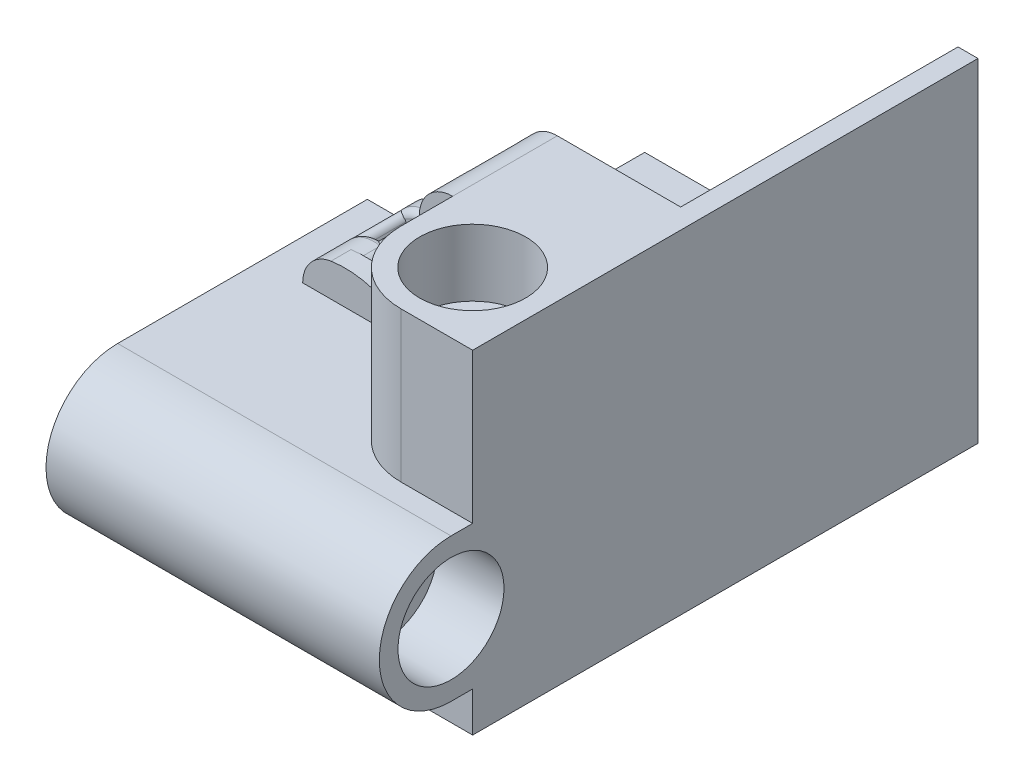
SolidWorks part; units mm, degrees
material "ABS"
ref_plane "Front Plane" through (0, 0, 0) normal (0, 0, 1) x (1, 0, 0)
ref_plane "Top Plane" through (0, 0, 0) normal (0, 1, 0) x (1, 0, 0)
ref_plane "Right Plane" through (0, 0, 0) normal (1, 0, 0) x (0, 0, -1)
sketch "Sketch1" plane through (0, 0, 0) normal (0, 0, 1) x (1, 0, 0)
  line L1 (-25, -25) -> (25, -25)
  line L2 (-25, -25) -> (-25, 25)
  line L3 (-25, 25) -> (25, 25)
  line L4 (25, -25) -> (25, 25)
  line L5 (-25, -25) -> (25, 25) construction
  line L6 (-25, 25) -> (25, -25) construction
  point P0 (0, 0)
  dimension "D1" = 50
  dimension "D2" = 50
extrude "Boss-Extrude1" add sketch "Sketch1" along normal blind 5
sketch "Sketch2" plane through (0, 0, 0) normal (0, 1, 0) x (1, 0, 0)
  line L0 (14.25, -15.75) -> (25, -15.75) construction
  line L1 (3.5, -5) -> (25, -5)
  line L2 (25, -5) -> (-25, -5) construction
  line L3 (25, -5) -> (25, 0) construction
  line L4 (25, -15.75) -> (25, -5)
  line L5 (3.5, -15.75) -> (3.5, -5)
  line L6 (25, -15.75) -> (25, -26.5)
  line L7 (25, -26.5) -> (14.25, -26.5)
  arc A1 (3.5, -15.75) -> (14.25, -26.5) centre (14.25, -15.75) ccw
  dimension "D2" = 21.5
extrude "Boss-Extrude2" add sketch "Sketch2" along normal up to surface and the other way up to surface up to face at (0, 25, 2.5) other way up to face at (0, -25, 2.5)
ref_axis "Axis1" through (14.25, 25, 15.75) along (0, -1, 0)
sketch "Sketch3" plane through (0, 0, 0) normal (1, 0, 0) x (0, 0, -1)
  line L0 (-29.75, 2.5) -> (-5, 2.5)
  line L1 (-5, 25) -> (-5, -25) construction
  line L2 (-29.75, -19) -> (-5, -19)
  line L3 (-5, 25) -> (-5, -25) construction
  line L4 (-5, -19) -> (-5, 2.5)
  line L5 (-15.75, 25) -> (-15.75, -25) construction
  line L6 (-15.75, -25) -> (-5, -25) construction
  arc A0 (-29.75, 2.5) -> (-29.75, -19) centre (-29.75, -8.25) ccw
  dimension "D1" = 21.5
  dimension "D2" = 14
  dimension "D3" = 6
extrude "Boss-Extrude3" add sketch "Sketch3" along normal up to surface and the other way up to surface up to face at (25, 0, 13.25) other way up to face at (-25, 0, 2.5)
ref_axis "Axis2" through (25, -8.25, 29.75) along (-1, 0, 0)
sketch "Sketch4" plane through (0, -25, 0) normal (0, -1, 0) x (1, 0, 0)
  circle A0 centre (14.25, 15.75) radius 5
  dimension "D1" = 10
extrude "Cut-Extrude1" cut sketch "Sketch4" against normal up to surface (50 mm away) up to face at (4.7534, 25, 12.3359)
sketch "Sketch5" plane through (0, -25, 0) normal (0, -1, 0) x (1, 0, 0)
  circle A0 centre (14.25, 15.75) radius 7.95
  dimension "D1" = 15.9
extrude "Cut-Extrude2" cut sketch "Sketch5" against normal blind 10
sketch "Sketch6" plane through (0, 25, 0) normal (0, 1, 0) x (1, 0, 0)
  circle A0 centre (14.25, -15.75) radius 7.95
  dimension "D1" = 15.9
extrude "Cut-Extrude3" cut sketch "Sketch6" against normal blind 10
sketch "Sketch7" plane through (25, 0, 0) normal (1, 0, 0) x (0, 0, -1)
  circle A0 centre (-29.75, -8.25) radius 5
  dimension "D1" = 10
extrude "Cut-Extrude4" cut sketch "Sketch7" against normal up to surface (50 mm away) up to face at (-25, -4.125, 11.2812)
sketch "Sketch8" plane through (25, 0, 0) normal (1, 0, 0) x (0, 0, -1)
  circle A0 centre (-29.75, -8.25) radius 7.95
  dimension "D1" = 15.9
extrude "Cut-Extrude5" cut sketch "Sketch8" against normal blind 10
sketch "Sketch9" plane through (-25, 0, 0) normal (-1, 0, 0) x (0, 0, 1)
  circle A0 centre (29.75, -8.25) radius 7.95
  dimension "D1" = 15.9
extrude "Cut-Extrude6" cut sketch "Sketch9" against normal blind 10
sketch "Sketch10" plane through (0, 0, 5) normal (0, 0, 1) x (1, 0, 0)
  line L0 (3.5, 2.5) -> (-5, 11) construction
  line L1 (3.5, 25) -> (-25, 25)
  line L2 (-25, 2.5) -> (-19, 2.5)
  line L4 (-25, 2.5) -> (3.5, 2.5)
  line L5 (3.5, 2.5) -> (3.5, 25)
  line L6 (3.5, 25) -> (-25, 25)
  line L7 (-25, 25) -> (-25, 2.5)
  line L8 (-25, 2.5) -> (3.5, 2.5)
  line L9 (3.5, 2.5) -> (3.5, 25)
  line L10 (3.5, 25) -> (-25, 25)
  line L11 (-25, 25) -> (-25, 2.5)
  arc A0 (-11.7656, 6.5462) -> (-0.5462, 17.7656) centre (-5, 11) ccw
  arc A1 (3.5, 25) -> (-1.4109, 19.0603) centre (3.5, 20) ccw
  arc A2 (-0.5462, 17.7656) -> (-1.4109, 19.0603) centre (0.5535, 19.4362) cw
  arc A3 (-19, 2.5) -> (-13.0603, 7.4109) centre (-14, 2.5) cw
  arc A4 (-11.7656, 6.5462) -> (-13.0603, 7.4109) centre (-13.4362, 5.4465) ccw
  line M5 (-25, 2.5) -> (3.5, 2.5)
  line M7 (3.5, 25) -> (-25, 25)
  line M8 (-25, 25) -> (-25, 2.5)
  dimension "D2" = 16.2
  dimension "D3" = 5
  dimension "D4" = 2
  dimension "D1" = 0
extrude "Cut-Extrude7" cut sketch "Sketch10" against normal up to surface (5 mm away) contours A4 A0 A2 A1 A3 M7 M8 M5 region at (-11.9115, 14.3488, 5) up to face at (0, 0, 0)
sketch "Sketch11" plane through (0, 0, 5) normal (0, 0, 1) x (1, 0, 0)
  line L0 (3.5, 2.5) -> (-5, 11) construction
  line L1 (3.5, 25) -> (3.5, 2.5) construction
  line L2 (3.5, 2.5) -> (-19, 2.5) construction
  line L3 (3.5, 25) -> (3.5, 2.5)
  line L4 (3.5, 2.5) -> (-19, 2.5)
  arc A0 (-7.0104, 6.422) -> (-0.422, 13.0104) centre (-5, 11) ccw
  arc A1 (-1.4425, 20.7559) -> (-0.422, 13.0104) centre (12.3966, 18.6394) ccw
  arc A2 (-14.7559, 7.4425) -> (-7.0104, 6.422) centre (-12.6394, -6.3966) cw
  arc A4 (3.5, 25) -> (-1.4109, 19.0603) centre (3.5, 20) ccw construction
  arc A10 (-13.0603, 7.4109) -> (-19, 2.5) centre (-14, 2.5) ccw construction
  arc A11 (3.5, 25) -> (-1.4425, 20.7559) centre (3.5, 20) ccw
  arc A12 (-14.7559, 7.4425) -> (-19, 2.5) centre (-14, 2.5) ccw
  dimension "D1" = 10
  dimension "D2" = 14
extrude "Boss-Extrude4" add sketch "Sketch11" along normal blind 3
sketch "Sketch14" plane through (25, 0, 0) normal (1, 0, 0) x (0, 0, -1)
  line L0 (-26.5, -25) -> (0, -25) construction
  line L1 (0, 25) -> (49.3, 25)
  line L2 (0, 25) -> (0, -25)
  line L3 (0, -25) -> (49.3, -25)
  line L4 (49.3, 25) -> (49.3, -25)
  line L5 (49.3, -11.0918) -> (49.3, -12) construction
extrude "Boss-Extrude6" add sketch "Sketch14" against normal blind 3
sketch "Sketch15" plane through (0, 0, 0) normal (0, 0, -1) x (-1, 0, 0)
  line L0 (-13.95, -15.2) -> (-16.5, -15.2) construction
  line L1 (-22, -25) -> (-16.5, -25)
  line L2 (-22, -25) -> (-22, -15.2)
  line L3 (-22, -15.2) -> (-16.5, -15.2)
  line L4 (-16.5, -25) -> (-16.5, -15.2)
  line L5 (-12, -15.2) -> (-15.9, -15.2) construction
  line L6 (-16, -14.938) -> (-16, -27.1841) construction
  dimension "D1" = 0.5
extrude "Boss-Extrude7" add sketch "Sketch15" along normal up to surface (49.3 mm away) up to face at (23.5, 0, -49.3)
sketch "Sketch16" plane through (0, -15.2, 0) normal (0, 1, 0) x (1, 0, 0)
  line L1 (22, 0) -> (-25, 0)
  line L2 (22, 0) -> (22, 49.3)
  line L3 (22, 49.3) -> (-25, 49.3)
  line L4 (-25, 0) -> (-25, 49.3)
  line L5 (16.5, 49.3) -> (22, 49.3) construction
  line L7 (-25, -5) -> (-25, 0) construction
extrude "Boss-Extrude8" add sketch "Sketch16" along normal blind 3
sketch "Sketch17" plane through (0, 0, 0) normal (0, 0, -1) x (-1, 0, 0)
  line L5 (-22, -12.2) -> (25, -12.2)
  line L6 (25, -12.2) -> (25, 2.5)
  line L7 (25, 2.5) -> (19, 2.5)
  line L8 (-3.5, 25) -> (-22, 25)
  line L9 (-22, 25) -> (-22, -12.2)
  line L10 (-22, -12.2) -> (25, -12.2)
  line L11 (25, -12.2) -> (25, 2.5)
  line L12 (25, 2.5) -> (19, 2.5)
  line L13 (-3.5, 25) -> (-22, 25)
  line L14 (-22, 25) -> (-22, -12.2)
  arc A5 (19, 2.5) -> (13.0603, 7.4109) centre (14, 2.5) ccw
  arc A6 (13.0603, 7.4109) -> (11.7656, 6.5462) centre (13.4362, 5.4465) ccw
  arc A7 (0.5462, 17.7656) -> (11.7656, 6.5462) centre (5, 11) ccw
  arc A8 (0.5462, 17.7656) -> (1.4109, 19.0603) centre (-0.5535, 19.4362) ccw
  arc A9 (1.4109, 19.0603) -> (-3.5, 25) centre (-3.5, 20) ccw
  arc A10 (19, 2.5) -> (13.0603, 7.4109) centre (14, 2.5) ccw
  arc A11 (13.0603, 7.4109) -> (11.7656, 6.5462) centre (13.4362, 5.4465) ccw
  arc A12 (0.5462, 17.7656) -> (11.7656, 6.5462) centre (5, 11) ccw
  arc A13 (0.5462, 17.7656) -> (1.4109, 19.0603) centre (-0.5535, 19.4362) ccw
  arc A14 (1.4109, 19.0603) -> (-3.5, 25) centre (-3.5, 20) ccw
  dimension "D1" = 0
extrude "Boss-Extrude9" add sketch "Sketch17" along normal blind 7.7
ref_plane "Plane1" through (0, 0, 1.3) normal (0, 0, -1) x (-1, 0, 0)
ref_plane "Plane2" through (0, 0, -4.7) normal (0, 0, 1) x (1, 0, 0)
sketch "Sketch18" plane through (0, 0, 1.3) normal (0, 0, -1) x (-1, 0, 0)
  line L0 (0.722, 15.278) -> (-0.7276, 16.7276)
  line L1 (-1.05, 11) -> (23.1459, 11) construction
  line L2 (9.278, 6.722) -> (10.7276, 5.2724)
  arc A0 (0.722, 15.278) -> (9.278, 6.722) centre (5, 11) ccw
  arc A1 (0.5462, 17.7656) -> (11.7656, 6.5462) centre (5, 11) ccw construction
  arc A2 (-0.7276, 16.7276) -> (10.7276, 5.2724) centre (5, 11) ccw
  dimension "D1" = 12.1
  dimension "D2" = 45
  dimension "D3" = 180
extrude "Boss-Extrude10" add sketch "Sketch18" along normal up to surface (6 mm away) up to plane "Plane2"
ref_plane "Plane3" through (-5, 0, 0) normal (-1, 0, 0) x (0, 0, 1)
sketch "Sketch19" plane through (-5, 0, 0) normal (-1, 0, 0) x (0, 0, 1)
  line L0 (1.3, 8.8) -> (1.3, -8.8) construction
  line L1 (1.3, 21.5) -> (-4.7, 21.5)
  line L2 (1.3, 21.5) -> (1.3, 23.5)
  line L3 (1.3, 23.5) -> (-4.7, 23.5)
  line L4 (-4.7, 21.5) -> (-4.7, 23.5)
  line L5 (-4.7, -8.8) -> (-4.7, 8.8) construction
  line L6 (16.2565, 11) -> (-48.8952, 11) construction
  dimension "D1" = 10.5
  dimension "D2" = 2
ref_axis "Axis3" through (-5, 11, 8) along (0, 0, -1)
revolve "Cut-Revolve1" cut sketch "Sketch19" angle 360 about axis through (-5, 11, 8) along (0, 0, -1)
fillet "Fillet1" radius 1 8 edges at (-16.7325, 6.6873, -1.7) (-15.8395, 7.1493, -4.7) (-14.8721, 7.4234, -1.7) (-15.8395, 7.1493, 1.3) (-1.1493, 21.8395, 1.3) (-0.6873, 22.7325, -1.7) (-1.1493, 21.8395, -4.7) (-1.4234, 20.8721, -1.7)
